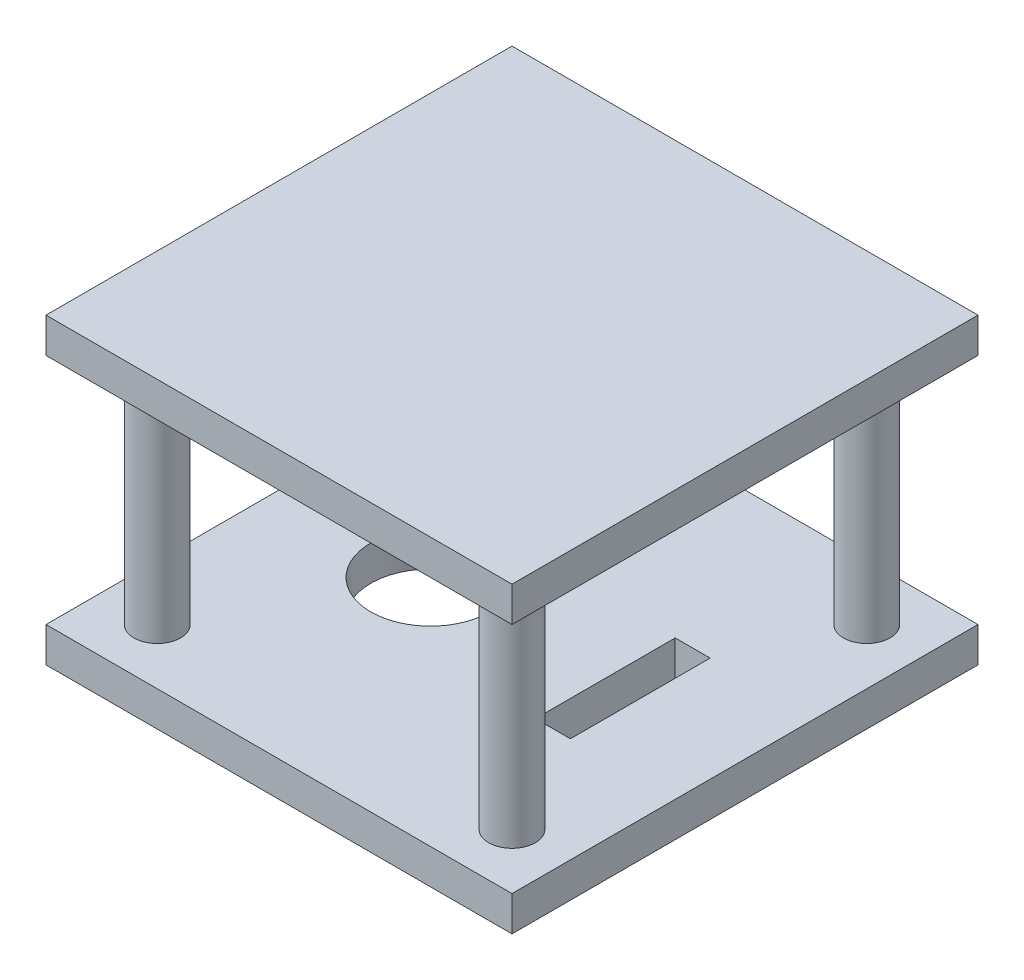
SolidWorks part; units mm, degrees
ref_plane "前视基准面" through (0, 0, 0) normal (0, 0, 1) x (1, 0, 0)
ref_plane "上视基准面" through (0, 0, 0) normal (0, 1, 0) x (1, 0, 0)
ref_plane "右视基准面" through (0, 0, 0) normal (1, 0, 0) x (0, 0, -1)
sketch "草图2" plane through (0, 0, 0) normal (0, 1, 0) x (1, 0, 0)
  line L0 (0, 0) -> (31.047, 0) construction
  line L1 (-9.75, -9.75) -> (9.75, -9.75)
  line L2 (-9.75, -9.75) -> (-9.75, 9.75)
  line L3 (-9.75, 9.75) -> (9.75, 9.75)
  line L4 (9.75, -9.75) -> (9.75, 9.75)
  line L5 (-9.75, -9.75) -> (9.75, 9.75) construction
  line L6 (-9.75, 9.75) -> (9.75, -9.75) construction
  line L7 (-20, -20) -> (20, -20)
  line L8 (-20, -20) -> (-20, 20)
  line L9 (-20, 20) -> (20, 20)
  line L10 (20, -20) -> (20, 20)
  line L11 (-20, -20) -> (20, 20) construction
  line L12 (-20, 20) -> (20, -20) construction
  line L13 (0, 0) -> (0, 17.7315) construction
  circle A0 centre (15.2248, 15.2248) radius 2
  circle A1 centre (-15.2248, -15.2248) radius 2
  circle A2 centre (15.2248, -15.2248) radius 2
  circle A3 centre (-15.2248, 15.2248) radius 2
  point P0 (0, 0)
  point P6 (0, 0)
  point P22 (20, -20)
  dimension "D5" = 4
  dimension "D1" = 19.5
  dimension "D2" = 19.5
  dimension "D3" = 40
  dimension "D4" = 40
  dimension "D6" = 21.5311
extrude "凸台-拉伸2" add sketch "草图2" along normal blind 3 contours L8 L9 L10 L7
sketch "草图3" plane through (0, 0, 0) normal (0, 1, 0) x (1, 0, 0)
  line L7 (8, 6.0116) -> (11, 6.0116)
  line L8 (8, 6.0116) -> (8, -5.9884)
  line L9 (8, -5.9884) -> (11, -5.9884)
  line L10 (11, 6.0116) -> (11, -5.9884)
  circle A0 centre (-15.2248, -15.2248) radius 2 construction
  circle A1 centre (15.2248, -15.2248) radius 2 construction
  circle A2 centre (15.2248, 15.2248) radius 2 construction
  circle A3 centre (-15.2248, 15.2248) radius 2 construction
  circle A4 centre (-15.2248, -15.2248) radius 2
  circle A5 centre (15.2248, -15.2248) radius 2
  circle A6 centre (15.2248, 15.2248) radius 2
  circle A7 centre (-15.2248, 15.2248) radius 2
  circle A8 centre (-7, 0) radius 5.125
  point P27 (8, 0.0116)
  dimension "D1" = 10.25
  dimension "D2" = 8
  dimension "D5" = 12
  dimension "D6" = 3
extrude "切除-拉伸1" cut sketch "草图3" along normal blind 3
sketch "草图4" plane through (0, 0, 0) normal (0, 1, 0) x (1, 0, 0)
  line L0 (0, 0) -> (31.047, 0) construction
  circle A0 centre (3, 0) radius 2
  dimension "D1" = 4
  dimension "D2" = 3
sketch "草图9" plane through (0, 3, 0) normal (0, 1, 0) x (1, 0, 0)
  line L1 (20, -20) -> (-20, -20)
  line L2 (20, -20) -> (20, 20)
  line L3 (20, 20) -> (-20, 20)
  line L4 (-20, -20) -> (-20, 20)
extrude "凸台-拉伸4" add sketch "草图9" along normal blind 3 from offset 20 separate body
extrude "凸台-拉伸5" add sketch "草图3<3>" along normal blind 24 contours A4 | A7 | A6 | A5
sketch "草图3<3>" plane through (0, 0, 0) normal (0, 1, 0) x (1, 0, 0) same geometry as "草图3"
extrude "凸台-拉伸6" add sketch "草图2<8>" against normal blind 2 contours A0 | A3 | A1 | A2
sketch "草图2<8>" plane through (0, 0, 0) normal (0, 1, 0) x (1, 0, 0) same geometry as "草图2"
sketch "草图11" plane through (0, 23, 0) normal (0, -1, 0) x (1, 0, 0)
  line L1 (-14.325, -7.9352) -> (14.325, -7.9352)
  line L2 (-14.325, -7.9352) -> (-14.325, 7.9352)
  line L3 (-14.325, 7.9352) -> (14.325, 7.9352)
  line L4 (14.325, -7.9352) -> (14.325, 7.9352)
  line L5 (-14.325, -7.9352) -> (14.325, 7.9352) construction
  line L6 (-14.325, 7.9352) -> (14.325, -7.9352) construction
  point P0 (0, 0)
  point P6 (-14.325, -7.9352)
sketch "草图12" plane through (0, 3, 0) normal (0, 1, 0) x (1, 0, 0)
  circle A0 centre (-7, 0) radius 5.125 construction
  circle A1 centre (-7, 0) radius 5.125
sketch "草图16" plane through (0, 0, 0) normal (1, 0, 0) x (0, 0, -1)
  circle A0 centre (-4.3167, -2.2841) radius 0.8937
  circle A1 centre (-0.9811, -2.2841) radius 0.8937
  circle A2 centre (1.6678, -2.2841) radius 0.8937
  circle A3 centre (4.611, -2.2841) radius 0.8937
  point P4 (-0.9811, -2.2841)
  point P7 (1.6678, -2.2841)
  point P10 (4.611, -2.2841)
